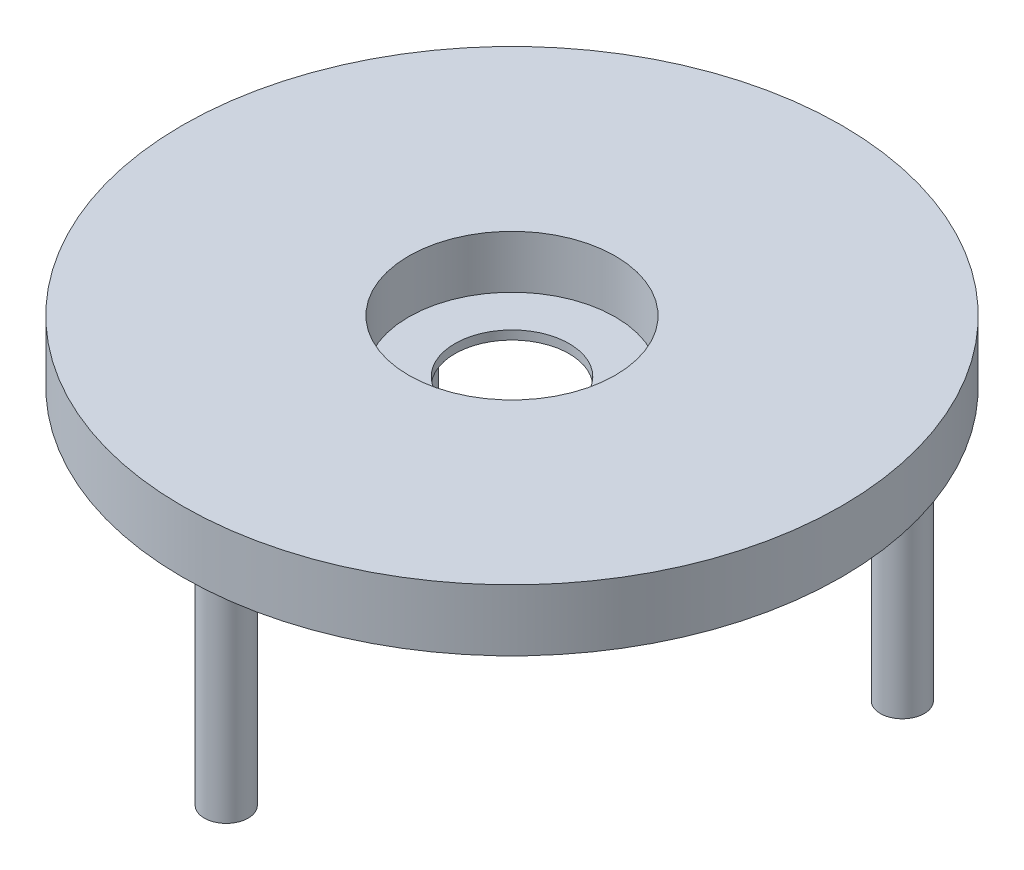
SolidWorks part; units mm, degrees
ref_plane "Płaszczyzna przednia" through (0, 0, 0) normal (0, 0, 1) x (1, 0, 0)
ref_plane "Płaszczyzna górna" through (0, 0, 0) normal (0, 1, 0) x (1, 0, 0)
ref_plane "Płaszczyzna prawa" through (0, 0, 0) normal (1, 0, 0) x (0, 0, -1)
sketch "Szkic4" plane through (0, 0, 0) normal (0, 1, 0) x (1, 0, 0)
  circle A0 centre (0, 0) radius 75
extrude "Dodanie-wyciągnięcie2" add sketch "Szkic4" along normal blind 14
sketch "Szkic5" plane through (0, 14, 0) normal (0, 1, 0) x (1, 0, 0)
  circle A0 centre (0, 0) radius 23.5
extrude "Wytnij-wyciągnięcie3" cut sketch "Szkic5" against normal blind 12
sketch "Szkic6" plane through (0, 2, 0) normal (0, 1, 0) x (1, 0, 0)
  circle A0 centre (0, 0) radius 13
  dimension "D1" = 26
extrude "Wytnij-wyciągnięcie4" cut sketch "Szkic6" against normal blind 12
sketch "Szkic7" plane through (0, 0, 0) normal (0, -1, 0) x (-1, 0, 0)
  circle A0 centre (0, -65) radius 5
  circle A1 centre (-56.2917, 32.5) radius 5
  circle A2 centre (56.2917, 32.5) radius 5
  point P10 (0, 0)
  dimension "D1" = 10
  dimension "D2" = 65
  dimension "D3" = 3
extrude "Dodanie-wyciągnięcie3" add sketch "Szkic7" along normal blind 50
